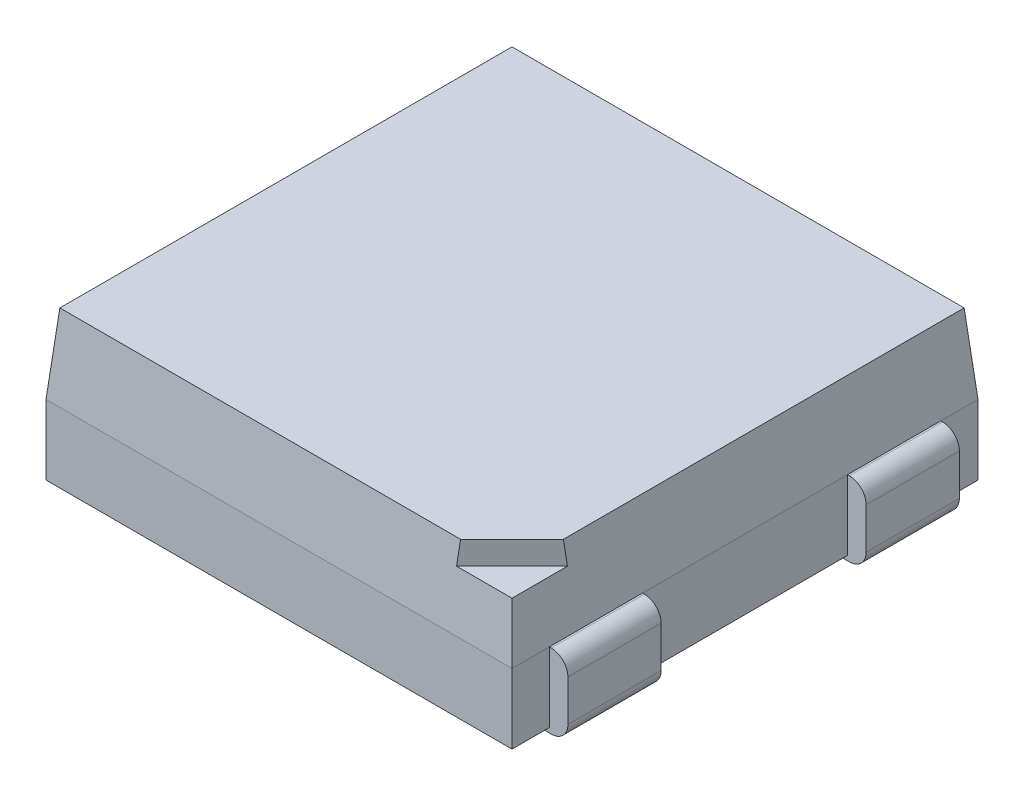
SolidWorks part; units mm, degrees
ref_plane "Front Plane" through (0, 0, 0) normal (0, 0, 1) x (1, 0, 0)
ref_plane "Top Plane" through (0, 0, 0) normal (0, 1, 0) x (1, 0, 0)
ref_plane "Right Plane" through (0, 0, 0) normal (1, 0, 0) x (0, 0, -1)
sketch "Sketch1" plane through (0, 0, 0) normal (0, 1, 0) x (1, 0, 0)
  line L0 (2.7, 5) -> (2.7, 0) construction
  line L1 (0, 0) -> (5.4, 0) construction
  line L2 (0, 0) -> (0, 5) construction
  line L3 (0, 5) -> (5.4, 5) construction
  line L4 (5.4, 0) -> (5.4, 5) construction
  line L5 (5.2, 5) -> (0.2, 5)
  line L6 (5.2, 5) -> (5.2, 0)
  line L7 (5.2, 0) -> (0.2, 0)
  line L8 (0.2, 5) -> (0.2, 0)
  line L9 (0, 2.5) -> (5.4, 2.5) construction
  line L10 (0, 4.6) -> (1, 4.6)
  line L11 (0, 4.6) -> (0, 3.6)
  line L12 (0, 3.6) -> (1, 3.6)
  line L13 (1, 4.6) -> (1, 3.6)
  line L14 (5.4, 3.6) -> (4.4, 3.6)
  line L15 (4.4, 4.6) -> (4.4, 3.6)
  line L16 (5.4, 4.6) -> (4.4, 4.6)
  line L17 (5.4, 4.6) -> (5.4, 3.6)
  line L18 (5.4, 0.4) -> (5.4, 1.4)
  line L19 (5.4, 0.4) -> (4.4, 0.4)
  line L20 (4.4, 0.4) -> (4.4, 1.4)
  line L21 (5.4, 1.4) -> (4.4, 1.4)
  line L22 (0, 1.4) -> (1, 1.4)
  line L23 (1, 0.4) -> (1, 1.4)
  line L24 (0, 0.4) -> (1, 0.4)
  line L25 (0, 0.4) -> (0, 1.4)
  point P9 (2.7, 5)
  point P10 (2.7, 5)
  dimension "D1" = 5.4
  dimension "D2" = 5
  dimension "D3" = 5
  dimension "D4" = 1
  dimension "D5" = 0.4
extrude "Boss-Extrude1" add sketch "Sketch1" along normal blind 0.75 contours L24 L8 L7 L6 L19 L20 L21 L14 L15 L16 L5 L10 L13 L12 L22 L23 | L13 L10 L8 L12 | L6 L16 L15 L14 | L6 L21 L20 L19 | L8 L24 L23 L22 region at (2.7, 0, -2.5) region at (4.8, 0, -4.1) region at (0.6, 0, -4.1) region at (4.8, 0, -0.9) region at (0.6, 0, -0.9)
extrude "Boss-Extrude3" add sketch "Sketch1<4>" along normal up to surface (0.75 mm away) and the other way blind 0.05 contours L25 L24 L8 L22 | L8 L24 L23 L22 | L11 L12 L8 L10 | L13 L10 L8 L12 | L6 L21 L20 L19 | L18 L21 L6 L19 | L6 L16 L15 L14 | L17 L16 L6 L14 region at (5.3, 0, -4.1) region at (4.8, 0, -4.1) region at (0.6, 0, -4.1) region at (0.1, 0, -4.1) region at (5.3, 0, -0.9) region at (4.8, 0, -0.9) region at (0.6, 0, -0.9) region at (0.1, 0, -0.9) up to face at (2.7, 0.75, -2.5)
sketch "Sketch1<4>" plane through (0, 0, 0) normal (0, 1, 0) x (1, 0, 0) same geometry as "Sketch1"
fillet "Fillet2" radius 0.18 8 edges at (5.4, 0.75, -0.9) (5.4, 0.75, -4.1) (0, 0.75, -0.9) (0, 0.75, -4.1) (5.4, -0.05, -4.1) (5.4, -0.05, -0.9) (0, -0.05, -0.9) (0, -0.05, -4.1)
sketch "Sketch4" plane through (0, 0.75, 0) normal (0, 1, 0) x (1, 0, 0)
  line L0 (4.5, 0) -> (5.2, 0.7)
  line L1 (5.2, 0) -> (0.2, 0) construction
  line L2 (5.2, 0.7) -> (5.2, 0)
  line L3 (5.2, 0) -> (4.5, 0)
  dimension "D1" = 0.7
sketch "Sketch2" plane through (0, 0.75, 0) normal (0, 1, 0) x (1, 0, 0)
  line L0 (0.2, 4.6) -> (0.2, 3.6)
  line L1 (0.2, 1.4) -> (0.2, 0.4)
  line L2 (5.2, 4.6) -> (5.2, 3.6)
  line L3 (5.2, 1.4) -> (5.2, 0.4)
  line L4 (5.2, 0) -> (5.2, 0.4)
  line L5 (5.2, 5) -> (0.2, 5)
  line L6 (0.2, 5) -> (0.2, 4.6)
  line L7 (0.2, 0) -> (5.2, 0)
  line L8 (5.2, 0) -> (5.2, 0.4)
  line L9 (5.2, 5) -> (0.2, 5)
  line L10 (0.2, 5) -> (0.2, 4.6)
  line L11 (0.2, 0) -> (5.2, 0)
  line L28 (5.2, 1.4) -> (5.2, 3.6)
  line L29 (5.2, 1.4) -> (5.2, 3.6)
  line L30 (5.2, 3.6) -> (5.22, 3.6)
  line L32 (5.22, 0.4) -> (5.22, 1.4)
  line L34 (5.22, 4.6) -> (5.2, 4.6)
  line L36 (5.2, 4.6) -> (5.2, 5)
  line L37 (5.2, 4.6) -> (5.2, 5)
  line L38 (0.2, 4.6) -> (0.18, 4.6)
  line L40 (5.22, 0.4) -> (5.22, 1.4)
  line L42 (0.18, 3.6) -> (0.2, 3.6)
  line L44 (0.2, 3.6) -> (0.2, 1.4)
  line L45 (0.2, 3.6) -> (0.2, 1.4)
  line L46 (0.2, 1.4) -> (0.18, 1.4)
  line L48 (5.22, 3.6) -> (5.22, 4.6)
  line L50 (0.18, 0.4) -> (0.2, 0.4)
  line L52 (0.2, 0.4) -> (0.2, 0)
  line L53 (0.2, 0.4) -> (0.2, 0)
  line L54 (5.2, 0.4) -> (5.22, 0.4)
  line L56 (5.22, 3.6) -> (5.22, 4.6)
  line L58 (5.22, 1.4) -> (5.2, 1.4)
  line L64 (0.18, 4.6) -> (0.18, 3.6)
  line L65 (0.18, 4.6) -> (0.18, 3.6)
  line L66 (0.18, 1.4) -> (0.18, 0.4)
  line L67 (0.18, 1.4) -> (0.18, 0.4)
  line M5 (5.2, 0) -> (5.2, 0.4)
  line M6 (5.2, 5) -> (0.2, 5)
  line M7 (0.2, 5) -> (0.2, 4.6)
  line M8 (0.2, 0) -> (5.2, 0)
  line M9 (5.2, 1.4) -> (5.2, 3.6)
  line M13 (5.2, 4.6) -> (5.2, 5)
  line M17 (0.2, 3.6) -> (0.2, 1.4)
  line M21 (0.2, 0.4) -> (0.2, 0)
  dimension "D1" = 0
extrude "Boss-Extrude2" add sketch "Sketch2" along normal blind 0.85 draft 5 contours L3 L2 L0 L1 M9 M13 M6 M7 M17 M21 M8 M5 region at (2.7, 0.75, -2.5)
extrude "Cut-Extrude1" cut sketch "Sketch4" along normal up to surface (0.85 mm away) from offset 0.6 up to face at (2.7, 1.6, -2.5)
